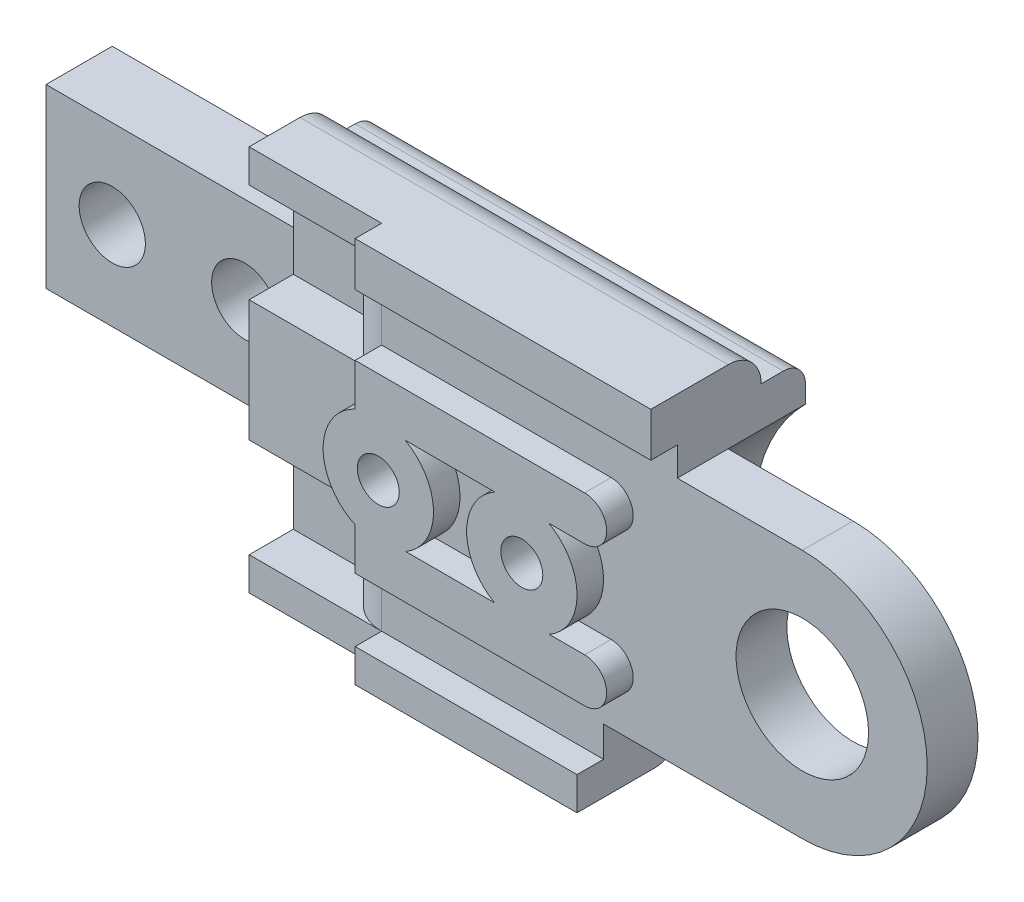
SolidWorks part; units mm, degrees
ref_plane "Front Plane" through (0, 0, 0) normal (0, 0, 1) x (1, 0, 0)
ref_plane "Top Plane" through (0, 0, 0) normal (0, 1, 0) x (1, 0, 0)
ref_plane "Right Plane" through (0, 0, 0) normal (1, 0, 0) x (0, 0, -1)
sketch "Sketch2" plane through (0, 0, 0) normal (0, 0, 1) x (1, 0, 0)
  line L0 (0, 0) -> (30, 0) construction
  line L3 (4.95, 7.4569) -> (24.3431, 7.4569)
  line L4 (24.3431, 5.6569) -> (24.3431, 7.4569)
  line L5 (24.3431, 5.6569) -> (30, 0) construction
  line L6 (22, 0) -> (21, -2.5431)
  line L7 (21, -2.5431) -> (21, -7.0431)
  line L8 (21, -7.0431) -> (8.4997, -7.0431)
  line L11 (4.95, 7.4569) -> (4.95, -7.0431)
  line L12 (8.4997, -7.0431) -> (4.95, -7.0431)
  arc A2 (24.3431, 5.6569) -> (22, 0) centre (30, 0) ccw
  point P3 (21, -4.7931)
  dimension "D1" = 16.05
  dimension "D2" = 14.5
  dimension "D5" = 45
  dimension "D6" = 16
  dimension "D3" = 1.8
  dimension "D4" = 30
  dimension "D7" = 1
  dimension "D8" = 4.5
extrude "Boss-Extrude1" add sketch "Sketch2" along normal blind 2
sketch "Sketch3" plane through (0, 0, 2) normal (0, 0, 1) x (1, 0, 0)
  line L0 (24.3431, 7.4569) -> (24.3431, 5.6569)
  line L1 (22, 0) -> (21, -2.5431)
  line L2 (21, -2.5431) -> (22, 0) construction
  line L3 (21, -2.5431) -> (21, -7.0431)
  line L6 (4.95, 8.9569) -> (4.95, -8.5431)
  line L12 (4.95, 8.9569) -> (24.3431, 8.9569)
  line L13 (24.3431, 8.9569) -> (24.3431, 7.4569)
  line L15 (4.95, -8.5431) -> (21, -8.5431)
  line L16 (21, -8.5431) -> (21, -7.0431)
  line L17 (4.95, 7.4569) -> (4.95, -7.0431) construction
  line L18 (24.3431, 7.4569) -> (4.95, 7.4569) construction
  line L21 (4.95, -7.0431) -> (21, -7.0431) construction
  arc A0 (24.3431, 5.6569) -> (22, 0) centre (30, 0) ccw
  arc A1 (24.3431, 5.6569) -> (22, 0) centre (30, 0) ccw construction
  dimension "D1" = 1.5
  dimension "D2" = 1.5
extrude "Boss-Extrude2" add sketch "Sketch3" along normal blind 1.5
ref_plane "Plane1" through (0, 0, 3.5) normal (0, 0, 1) x (1, 0, 0)
sketch "Sketch5" plane through (0, 0, 3.5) normal (0, 0, 1) x (1, 0, 0)
  line L4 (4.95, -8.5431) -> (21, -8.5431)
  line L6 (24.3431, 7.5) -> (24.3431, 5.6569)
  line L7 (24.3431, 5.6569) -> (30.0031, 5.6569)
  line L8 (30.0031, -5.6569) -> (21, -5.6569)
  line L9 (21, -8.5431) -> (21, -2.5431) construction
  line L10 (21, -5.6569) -> (21, -8.5431)
  line L12 (4.95, 8.9569) -> (24.3431, 8.9569)
  line L13 (24.3431, 8.9569) -> (24.3431, 7.5)
  line L17 (4.95, 8.9569) -> (4.95, -8.5431)
  line L18 (4.95, 8.9569) -> (4.95, -8.5431) construction
  line L19 (4.95, -8.5431) -> (21, -8.5431) construction
  arc A0 (30.0031, -5.6569) -> (30.0031, 5.6569) centre (30.0031, 0) ccw
  dimension "D1" = 5.66
extrude "Boss-Extrude3" add sketch "Sketch5" along normal blind 2.3 contours A0 L7 L6 L13 L12 L17 L4 L10 L8
sketch "Sketch6" plane through (0, 0, 5.8) normal (0, 0, 1) x (1, 0, 0)
  line L0 (4.95, 2.9569) -> (4.95, 7.4569)
  line L1 (4.95, 2.9569) -> (8.95, 2.9569)
  line L2 (4.95, 7.4569) -> (8.95, 7.4569)
  line L3 (8.95, 2.9569) -> (8.95, 7.4569)
  line L5 (4.95, 8.9569) -> (24.3431, 8.9569) construction
  line L6 (4.95, -7.0431) -> (4.95, -2.5431)
  line L7 (4.95, -7.0431) -> (8.95, -7.0431)
  line L8 (4.95, -2.5431) -> (8.95, -2.5431)
  line L9 (8.95, -7.0431) -> (8.95, -2.5431)
  line L11 (4.95, -8.5431) -> (21, -8.5431) construction
  line L12 (4.95, 8.9569) -> (4.95, -8.5431) construction
  dimension "D1" = 4.5
  dimension "D2" = 1.5
  dimension "D3" = 4
  dimension "D4" = 1.5
  dimension "D5" = 4.5
extrude "Cut-Extrude1" cut sketch "Sketch6" against normal blind 2
sketch "Sketch7" plane through (0, 0, 5.8) normal (0, 0, 1) x (1, 0, 0)
  circle A0 centre (30.0031, 0) radius 3
  dimension "D1" = 6
extrude "Cut-Extrude2" cut sketch "Sketch7" against normal blind 3.3
sketch "Sketch8" plane through (0, 0, 5.8) normal (0, 0, 1) x (1, 0, 0)
  line L0 (24.3431, 8.9569) -> (10.95, 8.9569)
  line L1 (4.95, -8.5431) -> (21, -8.5431) construction
  line L2 (10.95, 8.9569) -> (10.95, 6.9569)
  line L3 (10.95, 6.9569) -> (24.3431, 6.9569)
  line L4 (24.3431, 8.9569) -> (24.3431, 5.6569) construction
  line L5 (24.3431, 6.9569) -> (24.3431, 8.9569)
  line L6 (21, -8.5431) -> (21, -7.0431)
  line L7 (21, -8.5431) -> (10.95, -8.5431)
  line L8 (10.95, -8.5431) -> (10.95, -7.0431)
  line L9 (10.95, -7.0431) -> (21, -7.0431)
  line L10 (10.95, -4.1721) -> (21.3431, -4.1721)
  line L12 (10.95, -2.1721) -> (10.95, -4.1721)
  line L13 (4.95, 8.9569) -> (24.3431, 8.9569) construction
  line L14 (8.95, 2.9569) -> (8.95, 7.4569) construction
  line L15 (21.3431, -2.1721) -> (10.95, -2.1721)
  line L16 (21.3431, 4.1803) -> (10.95, 4.1803)
  line L17 (10.95, 4.1803) -> (10.95, 2.1803)
  line L18 (10.95, 2.1803) -> (21.3431, 2.1803)
  arc A0 (21.3431, -4.1721) -> (21.3431, -2.1721) centre (21.3431, -3.1721) ccw
  arc A1 (21.3431, 2.1803) -> (21.3431, 4.1803) centre (21.3431, 3.1803) ccw
  dimension "D2" = 1
  dimension "D5" = 3
  dimension "D7" = 1
  dimension "D1" = 2
  dimension "D3" = 2
  dimension "D4" = 2
  dimension "D6" = 3
  dimension "D8" = 4.3524
  dimension "D9" = 1.5
  dimension "D10" = 2
extrude "Boss-Extrude4" add sketch "Sketch8" along normal blind 1.2
sketch "Sketch9" plane through (0, 0, 5.8) normal (0, 0, 1) x (1, 0, 0)
  line L0 (21, -8.5431) -> (21, -7.0431) construction
  line L1 (24.3431, 5.6569) -> (30.0031, 5.6569) construction
  circle A0 centre (18.5, 0) radius 2.5
  circle A1 centre (12, 0) radius 2.5
  dimension "D3" = 5
  dimension "D4" = 5
  dimension "D1" = 6.5
  dimension "D2" = 2.5
  dimension "D5" = 5.6569
extrude "Boss-Extrude5" add sketch "Sketch9" along normal blind 1.2
sketch "Sketch10" plane through (0, 0, 7) normal (0, 0, 1) x (1, 0, 0)
  circle A0 centre (18.5, 0) radius 0.95
  circle A1 centre (12, 0) radius 0.95
extrude "Cut-Extrude3" cut sketch "Sketch10" against normal blind 8.2
sketch "Sketch11" plane through (0, 0, 0) normal (0, 0, -1) x (-1, 0, 0)
  circle A0 centre (-12, 0) radius 2
  circle A1 centre (-18.5, 0) radius 2
extrude "Cut-Extrude4" cut sketch "Sketch11" against normal blind 2.2
fillet "Fillet1" radius 1.5 2 edges at (14.6466, 8.9569, 2) (12.975, -8.5431, 2)
fillet "Fillet2" radius 1 2 edges at (12.975, -7.0431, 0) (14.6466, 7.4569, 0)
fillet "Fillet3" radius 2 2 edges at (8.95, -4.7931, 5.8) (8.95, 5.2069, 5.8)
sketch "Sketch12" plane through (4.95, 0, 0) normal (-1, 0, 0) x (0, 0, 1)
  line L0 (0, 0) -> (9.9095, 0) construction
sketch "Sketch13" plane through (4.95, 0, 0) normal (-1, 0, 0) x (0, 0, 1)
  line L0 (0, 4) -> (0, -4)
  line L1 (0, 4) -> (3, 4)
  line L2 (0, -4) -> (3, -4)
  line L3 (3, 4) -> (3, -4)
  line L4 (0, 6.4569) -> (0, -6.0431) construction
  line L5 (0, 0) -> (9.9095, 0) construction
  dimension "D1" = 8
  dimension "D2" = 4
  dimension "D3" = 3
extrude "Boss-Extrude6" add sketch "Sketch13" along normal blind 12
sketch "Sketch14" plane through (0, 0, 0) normal (0, 0, -1) x (-1, 0, 0)
  line L0 (7.05, 4) -> (7.05, -4) construction
  circle A0 centre (-1.95, 0) radius 1.5
  circle A1 centre (4.05, 0) radius 1.5
  dimension "D1" = 6
  dimension "D2" = 3
extrude "Cut-Extrude5" cut sketch "Sketch14" against normal blind 12
